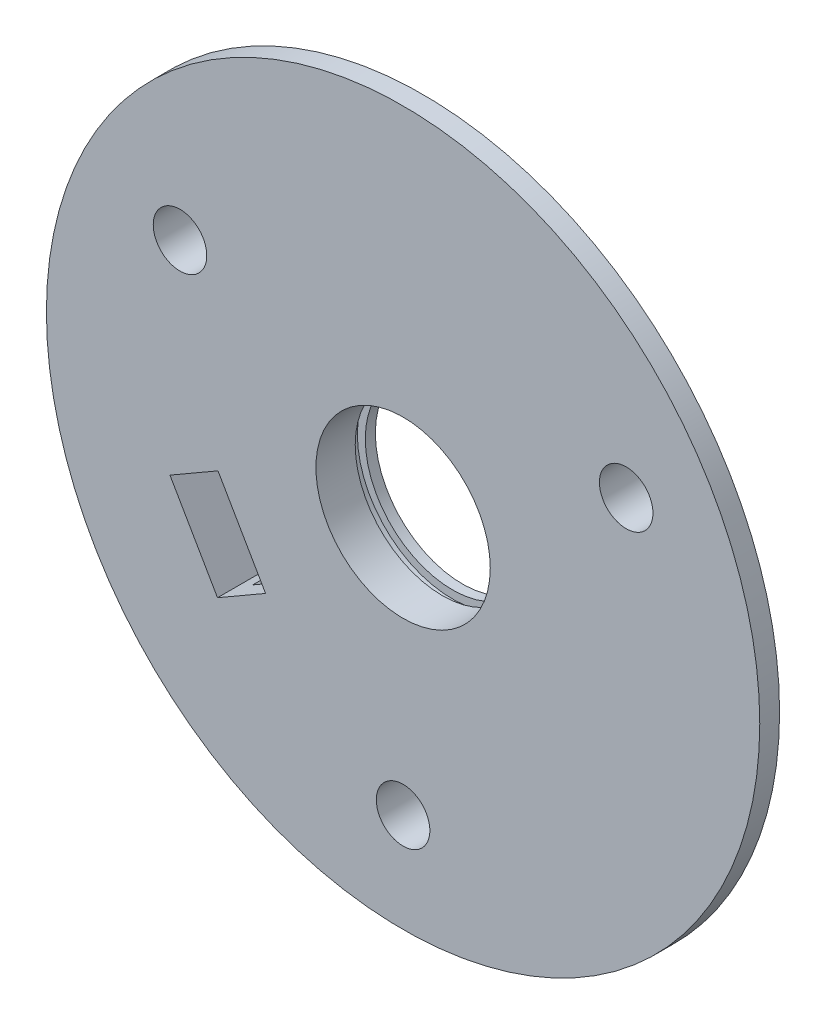
SolidWorks part; units mm, degrees
ref_plane "Front Plane" through (0, 0, 0) normal (0, 0, 1) x (1, 0, 0)
ref_plane "Top Plane" through (0, 0, 0) normal (0, 1, 0) x (1, 0, 0)
ref_plane "Right Plane" through (0, 0, 0) normal (1, 0, 0) x (0, 0, -1)
sketch "Sketch1" plane through (0, 0, 0) normal (0, 0, 1) x (1, 0, 0)
  circle A0 centre (0, 0) radius 45
  dimension "D1" = 90
extrude "Boss-Extrude1" add sketch "Sketch1" along normal blind 2.5 contours A0
sketch "Sketch2" plane through (0, 0, 2.5) normal (0, 0, 1) x (1, 0, 0)
  circle A0 centre (0, 0) radius 11
  dimension "D1" = 22
extrude "Cut-Extrude1" cut sketch "Sketch2" against normal blind 2.5
sketch "Sketch3" plane through (0, 0, 0) normal (0, 0, -1) x (-1, 0, 0)
  circle A0 centre (0, 0) radius 11
  circle A1 centre (0, 0) radius 13.5
  dimension "D1" = 22
  dimension "D2" = 27
extrude "Boss-Extrude2" add sketch "Sketch3" along normal blind 5 contours A1 | A0
ref_plane "Plane1" through (0, 0, -2.46) normal (0, 0, -1) x (-1, 0, 0)
sketch "Sketch5" plane through (0, 0, -2.46) normal (0, 0, -1) x (-1, 0, 0)
  circle A0 centre (0, 0) radius 12
  circle A1 centre (0, 0) radius 13.5 construction
  dimension "D1" = 24
extrude "Cut-Extrude2" cut sketch "Sketch5" along normal blind 1.27
sketch "Sketch6" plane through (0, 0, 0) normal (0, 0, -1) x (-1, 0, 0)
  circle A0 centre (0, 0) radius 40
  circle A1 centre (0, 0) radius 22.5
  dimension "D1" = 80
  dimension "D2" = 45
extrude "Boss-Extrude4" add sketch "Sketch6" along normal blind 3
sketch "Sketch10" plane through (0, 0, -3) normal (0, 0, -1) x (-1, 0, 0)
  circle A0 centre (0, 0) radius 32.5
  circle A1 centre (0, -32.5) radius 2.625
  circle A2 centre (-28.1458, 16.25) radius 2.625
  circle A3 centre (28.1458, 16.25) radius 2.625
  point P12 (0, 0)
  dimension "D1" = 65
  dimension "D2" = 5.25
  dimension "D3" = 3
fillet "Fillet1" radius 1 1 edges at (13.5, 0, 0)
sketch "Sketch12" plane through (0, 0, -3) normal (0, 0, -1) x (-1, 0, 0)
  line L0 (17.3516, -16.9462) -> (23.3516, -6.5538)
  line L1 (23.3516, -6.5538) -> (29.4138, -10.0538)
  line L2 (29.4138, -10.0538) -> (23.4138, -20.4462)
  line L3 (23.4138, -20.4462) -> (17.3516, -16.9462)
  line L4 (40.7032, -23.5) -> (0, 0)
  line L5 (-62.5, 0) -> (62.5, 0) construction
  point P2 (26.4138, -15.25)
  point P8 (20.3516, -11.75)
  dimension "D1" = 125
  dimension "D2" = 62.5
  dimension "D3" = 30
  dimension "D4" = 7
  dimension "D5" = 12
  dimension "D6" = 23.5
extrude "Cut-Extrude10" cut sketch "Sketch12" against normal through all contours L3 L0 L1 L2
sketch "Sketch13" plane through (0, 0, -3) normal (0, 0, -1) x (-1, 0, 0)
  line L0 (23.4138, -20.4462) -> (17.3516, -16.9462) construction
  line L1 (29.4138, -10.0538) -> (23.4138, -20.4462) construction
  line L2 (-1.75, -22) -> (1.75, -22)
  line L3 (19.3002, -18.0712) -> (21.4652, -19.3212)
  arc A0 (1.75, -22) -> (19.3002, -18.0712) centre (8.3254, -10.2096) ccw
  arc A1 (-1.75, -22) -> (21.4652, -19.3212) centre (8.5222, -9.0875) ccw
  point P0 (19.3002, -18.0712)
  point P1 (21.4652, -19.3212)
  dimension "D6" = 13.5
  dimension "D7" = 16.5
  dimension "D1" = 2.5
  dimension "D2" = 2.25
  dimension "D3" = 1.75
  dimension "D4" = 3.5
  dimension "D5" = 22
extrude "Cut-Extrude11" cut sketch "Sketch13" against normal up to surface (3 mm away) up to face at (14.5, 0, 0)
fillet "Fillet2" radius 2.5 1 edges at (0.6653, 22.4902, 0)
hole_wizard "H (0.266) Diameter Hole1" positions "Sketch14" profile "Sketch15" hole size "H" standard "ANSI Inch" end condition through all
sketch "Sketch14" plane through (0, 0, -3) normal (0, 0, -1) x (-1, 0, 0)
  point P0 (-28.1458, 16.25)
  point P3 (28.1458, 16.25)
  point P6 (0, -32.5)
sketch "Sketch15" plane through (28.1458, 16.25, -3) normal (1, 0, 0) x (0, 1, 0)
  line L0 (0, 0) -> (0, 5.5)
  line L1 (0, 5.5) -> (3.3782, 5.5)
  line L2 (3.3782, 5.5) -> (3.3782, 0)
  line L5 (3.3782, 0) -> (0, 0)
  line L11 (0, -6.35) -> (0, 107.95) construction
  dimension "Thru Hole Dia." = 6.7564
  dimension "Thru Hole Depth" = 5.5
